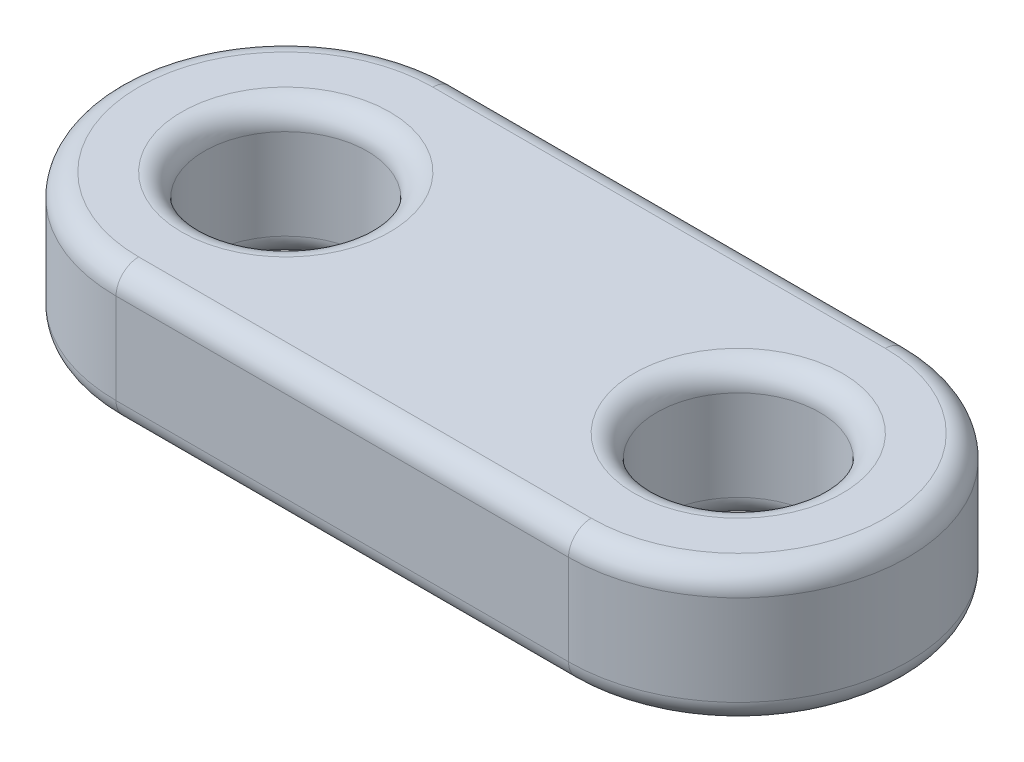
SolidWorks part; units mm, degrees
ref_plane "Front Plane" through (0, 0, 0) normal (0, 0, 1) x (1, 0, 0)
ref_plane "Top Plane" through (0, 0, 0) normal (0, 1, 0) x (1, 0, 0)
ref_plane "Right Plane" through (0, 0, 0) normal (1, 0, 0) x (0, 0, -1)
sketch "Sketch1" plane through (0, 0, 0) normal (0, 1, 0) x (1, 0, 0)
  line L0 (-5, 0) -> (5, 0) construction
  line L1 (-5, 3.75) -> (5, 3.75)
  line L2 (-5, -3.75) -> (5, -3.75)
  arc A0 (-5, 3.75) -> (-5, -3.75) centre (-5, 0) ccw
  arc A1 (5, -3.75) -> (5, 3.75) centre (5, 0) ccw
  point P3 (0, 0)
  dimension "D1" = 10
  dimension "D2" = 7.5
extrude "Boss-Extrude1" add sketch "Sketch1" along normal blind 3
hole_wizard "M3 Clearance Hole1" positions "Sketch2" profile "Sketch3" hole size "M3" standard "ANSI Metric" end condition through all
sketch "Sketch2" plane through (0, 0, 0) normal (0, 1, 0) x (1, 0, 0)
  point P0 (-5, 0)
  point P3 (5, 0)
sketch "Sketch3" plane through (-5, 0, 0) normal (1, 0, 0) x (0, 0, -1)
  line L0 (0, 0) -> (0, 3)
  line L1 (0, 3) -> (1.8, 3)
  line L2 (1.8, 3) -> (1.8, 0)
  line L5 (1.8, 0) -> (0, 0)
  line L11 (0, -6.35) -> (0, 107.95) construction
  dimension "Thru Hole Dia." = 3.6
  dimension "Thru Hole Depth" = 3
fillet "Fillet1" radius 0.5 12 edges at (0, 0, 3.75) (8.75, 0, 0) (0, 0, -3.75) (-8.75, 0, 0) (0, 3, -3.75) (8.75, 3, 0) (0, 3, 3.75) (-8.75, 3, 0) (5, 0, -1.8) (-5, 0, -1.8) (5, 3, -1.8) (-5, 3, -1.8)
